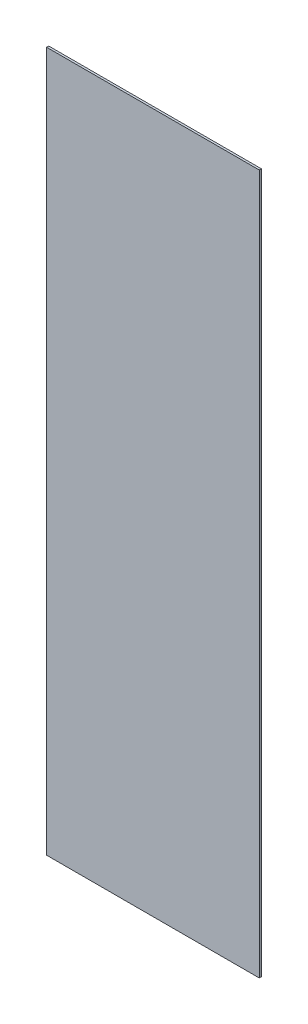
SolidWorks part; units mm, degrees
ref_plane "Спереди" through (0, 0, 0) normal (0, 0, 1) x (1, 0, 0)
ref_plane "Сверху" through (0, 0, 0) normal (0, 1, 0) x (1, 0, 0)
ref_plane "Справа" through (0, 0, 0) normal (1, 0, 0) x (0, 0, -1)
sketch "Эскиз1" plane through (0, 0, 0) normal (0, 0, 1) x (1, 0, 0)
  line L1 (13.5, -16.45) -> (23.5, -16.45)
  line L2 (13.5, -16.45) -> (13.5, 16.45)
  line L3 (13.5, 16.45) -> (23.5, 16.45)
  line L4 (23.5, -16.45) -> (23.5, 16.45)
  line L5 (13.5, -16.45) -> (23.5, 16.45) construction
  line L6 (13.5, 16.45) -> (23.5, -16.45) construction
  line L9 (-23.5, 16.75) -> (23.5, 16.75) construction
  line L10 (23.5, 16.75) -> (23.5, 14) construction
  point P0 (18.5, 0)
  point P7 (0, 0)
  dimension "D1" = 10
  dimension "D2" = 0.3
extrude "Бобышка-Вытянуть1" add sketch "Эскиз1" along normal blind 0.1
